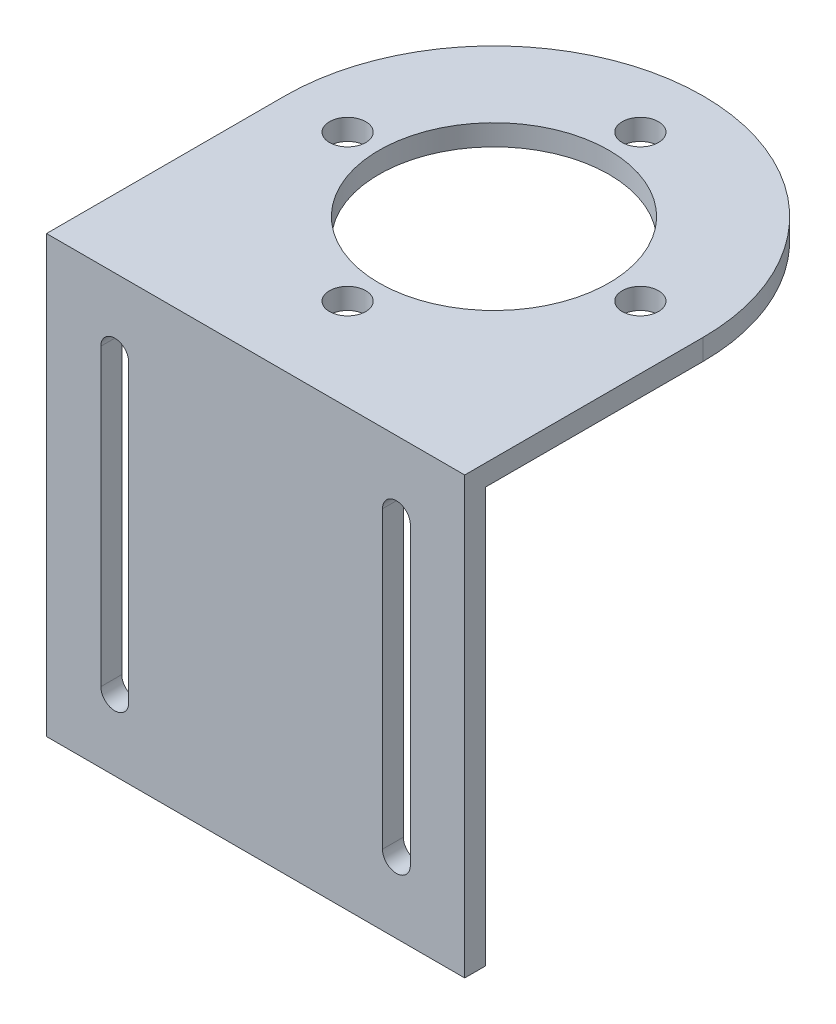
SolidWorks part; units mm, degrees
material "1023 Carbon Steel Sheet (SS)"
ref_plane "Front Plane" through (0, 0, 0) normal (0, 0, 1) x (1, 0, 0)
ref_plane "Top Plane" through (0, 0, 0) normal (0, 1, 0) x (1, 0, 0)
ref_plane "Right Plane" through (0, 0, 0) normal (1, 0, 0) x (0, 0, -1)
sketch "Sketch1" plane through (0, 0, 0) normal (0, 0, 1) x (1, 0, 0)
  line L0 (9.8, 10.1) -> (9.8, 52.4) construction
  line L1 (0, 0) -> (60, 0)
  line L2 (0, 0) -> (0, 62.5)
  line L3 (0, 62.5) -> (60, 62.5)
  line L4 (60, 0) -> (60, 62.5)
  line L5 (7.8, 10.1) -> (7.8, 52.4)
  line L6 (11.8, 10.1) -> (11.8, 52.4)
  line L7 (50.2, 10.1) -> (50.2, 52.4) construction
  line L8 (48.2, 10.1) -> (48.2, 52.4)
  line L9 (52.2, 10.1) -> (52.2, 52.4)
  arc A0 (7.8, 10.1) -> (11.8, 10.1) centre (9.8, 10.1) ccw
  arc A1 (11.8, 52.4) -> (7.8, 52.4) centre (9.8, 52.4) ccw
  arc A2 (48.2, 10.1) -> (52.2, 10.1) centre (50.2, 10.1) ccw
  arc A3 (52.2, 52.4) -> (48.2, 52.4) centre (50.2, 52.4) ccw
  point P7 (9.8, 31.25)
  point P13 (50.2, 31.25)
  point P20 (0, 31.25)
  point P22 (60, 31.25)
  dimension "D7" = 2
  dimension "D8" = 2
  dimension "D1" = 60
  dimension "D2" = 62.5
  dimension "D3" = 8.1
  dimension "D4" = 8.1
  dimension "D5" = 7.8
  dimension "D6" = 7.8
extrude "Boss-Extrude1" add sketch "Sketch1" along normal blind 3
sketch "Sketch2" plane through (0, 62.5, 0) normal (0, 1, 0) x (1, 0, 0)
  line L0 (60, -3) -> (60, 0) construction
  line L1 (0, -3) -> (60, -3)
  line L2 (0, -3) -> (0, 61.2)
  line L3 (0, 61.2) -> (60, 61.2)
  line L4 (60, -3) -> (60, 61.2)
  dimension "D1" = 64.2
extrude "Boss-Extrude2" add sketch "Sketch2" against normal blind 3
fillet "Fillet1" 2 edges at (0, 61, -61.2) (60, 61, -61.2) type full round first side face at (0, 40.6667, -19.4) second side face at (60, 40.6667, -19.4) middle face at (30, 61, -61.2)
sketch "Sketch3" plane through (0, 62.5, 0) normal (0, 1, 0) x (1, 0, 0)
  circle A0 centre (30, 31.2) radius 16.5
  arc A1 (60, 31.2) -> (0, 31.2) centre (30, 31.2) ccw construction
  circle A2 centre (30, 31.2) radius 21 construction
  circle A3 centre (30, 52.2) radius 2.6
  circle A4 centre (51, 31.2) radius 2.6
  circle A5 centre (30, 10.2) radius 2.6
  circle A6 centre (9, 31.2) radius 2.6
  point P8 (30, 31.2)
  point P17 (30, 31.2)
  dimension "D1" = 33
  dimension "D2" = 42
  dimension "D3" = 5.2
  dimension "D4" = 4
extrude "Cut-Extrude1" cut sketch "Sketch3" against normal blind 3
